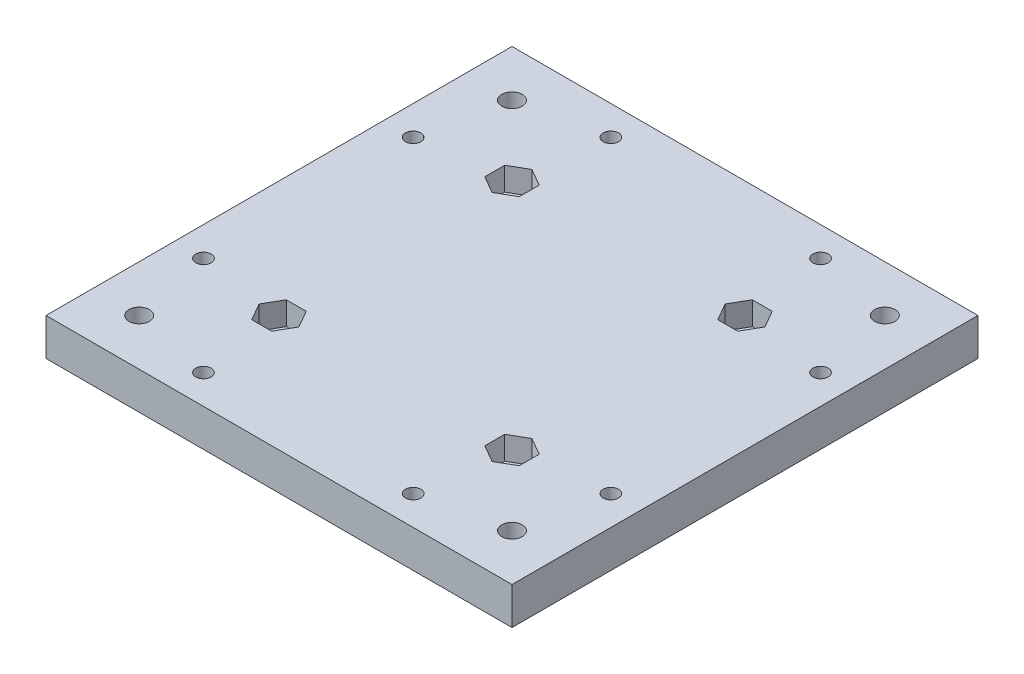
SolidWorks part; units mm, degrees
ref_plane "Front Plane" through (0, 0, 0) normal (0, 0, 1) x (1, 0, 0)
ref_plane "Top Plane" through (0, 0, 0) normal (0, 1, 0) x (1, 0, 0)
ref_plane "Right Plane" through (0, 0, 0) normal (1, 0, 0) x (0, 0, -1)
sketch "Sketch1" plane through (0, 0, 0) normal (0, 1, 0) x (1, 0, 0)
  line L0 (22.5, 43.7132) -> (43.7132, 22.5) construction
  line L1 (0, 0) -> (14.5501, 0) construction
  line L2 (28.7, -27.1362) -> (28.7, -22.8638)
  line L3 (27.1362, 28.7) -> (22.8638, 28.7)
  line L4 (22.8638, 28.7) -> (20.7276, 25)
  line L5 (20.7276, 25) -> (22.8638, 21.3)
  line L6 (22.8638, 21.3) -> (27.1362, 21.3)
  line L7 (27.1362, 21.3) -> (29.2724, 25)
  line L8 (29.2724, 25) -> (27.1362, 28.7)
  line L9 (42.1362, 36.3) -> (44.2724, 40)
  line L10 (44.2724, 40) -> (42.1362, 43.7)
  line L11 (42.1362, 43.7) -> (37.8638, 43.7)
  line L12 (37.8638, 43.7) -> (35.7276, 40)
  line L13 (35.7276, 40) -> (37.8638, 36.3)
  line L14 (37.8638, 36.3) -> (42.1362, 36.3)
  line L15 (28.7, -22.8638) -> (25, -20.7276)
  line L16 (25, -20.7276) -> (21.3, -22.8638)
  line L17 (21.3, -22.8638) -> (21.3, -27.1362)
  line L18 (21.3, -27.1362) -> (25, -29.2724)
  line L19 (25, -29.2724) -> (28.7, -27.1362)
  line L20 (36.3, -42.1362) -> (40, -44.2724)
  line L21 (40, -44.2724) -> (43.7, -42.1362)
  line L22 (43.7, -42.1362) -> (43.7, -37.8638)
  line L23 (43.7, -37.8638) -> (40, -35.7276)
  line L24 (40, -35.7276) -> (36.3, -37.8638)
  line L25 (36.3, -37.8638) -> (36.3, -42.1362)
  line L26 (-27.1362, -28.7) -> (-22.8638, -28.7)
  line L27 (-22.8638, -28.7) -> (-20.7276, -25)
  line L28 (-20.7276, -25) -> (-22.8638, -21.3)
  line L29 (-22.8638, -21.3) -> (-27.1362, -21.3)
  line L30 (-27.1362, -21.3) -> (-29.2724, -25)
  line L31 (-29.2724, -25) -> (-27.1362, -28.7)
  line L32 (-42.1362, -36.3) -> (-44.2724, -40)
  line L33 (-44.2724, -40) -> (-42.1362, -43.7)
  line L34 (-42.1362, -43.7) -> (-37.8638, -43.7)
  line L35 (-37.8638, -43.7) -> (-35.7276, -40)
  line L36 (-35.7276, -40) -> (-37.8638, -36.3)
  line L37 (-37.8638, -36.3) -> (-42.1362, -36.3)
  line L38 (-28.7, 27.1362) -> (-28.7, 22.8638)
  line L39 (-28.7, 22.8638) -> (-25, 20.7276)
  line L40 (-25, 20.7276) -> (-21.3, 22.8638)
  line L41 (-21.3, 22.8638) -> (-21.3, 27.1362)
  line L42 (-21.3, 27.1362) -> (-25, 29.2724)
  line L43 (-25, 29.2724) -> (-28.7, 27.1362)
  line L44 (-36.3, 42.1362) -> (-40, 44.2724)
  line L45 (-40, 44.2724) -> (-43.7, 42.1362)
  line L46 (-43.7, 42.1362) -> (-43.7, 37.8638)
  line L47 (-43.7, 37.8638) -> (-40, 35.7276)
  line L48 (-40, 35.7276) -> (-36.3, 37.8638)
  line L49 (-36.3, 37.8638) -> (-36.3, 42.1362)
  line L51 (-50, -50) -> (50, -50)
  line L52 (-50, -50) -> (-50, 50)
  line L53 (-50, 50) -> (50, 50)
  line L54 (50, -50) -> (50, 50)
  line L55 (-50, -50) -> (50, 50) construction
  line L56 (-50, 50) -> (50, -50) construction
  circle A0 centre (40, 40) radius 2.2
  circle A1 centre (43.7132, 22.5) radius 1.65
  circle A2 centre (22.5, 43.7132) radius 1.65
  circle A3 centre (25, 25) radius 2.15
  circle A4 centre (25, 25) radius 3.7 construction
  circle A5 centre (40, 40) radius 3.7 construction
  circle A6 centre (25, -25) radius 2.15
  circle A7 centre (22.5, -43.7132) radius 1.65
  circle A8 centre (40, -40) radius 2.2
  circle A9 centre (43.7132, -22.5) radius 1.65
  circle A10 centre (-25, -25) radius 2.15
  circle A11 centre (-43.7132, -22.5) radius 1.65
  circle A12 centre (-40, -40) radius 2.2
  circle A13 centre (-22.5, -43.7132) radius 1.65
  circle A14 centre (-25, 25) radius 2.15
  circle A15 centre (-22.5, 43.7132) radius 1.65
  circle A16 centre (-40, 40) radius 2.2
  circle A17 centre (-43.7132, 22.5) radius 1.65
  point P88 (0, 0)
  dimension "D3" = 4.4
  dimension "D6" = 3.3
  dimension "D7" = 3.3
  dimension "D8" = 30
  dimension "D10" = 4.3
  dimension "D1" = 40
  dimension "D2" = 40
  dimension "D4" = 22.5
  dimension "D5" = 22.5
  dimension "D9" = 45
  dimension "D11" = 25
  dimension "D12" = 25
  dimension "D13" = 7.4
  dimension "D14" = 7.4
  dimension "D16" = 100
  dimension "D15" = 4
extrude "Boss-Extrude1" add sketch "Sketch1" along normal blind 8 contours L51 L54 L53 L52 A17 A15 A13 A11 A9 A7 A2 A1 L8 L7 L6 L5 L4 L3 L14 L13 L12 L11 L10 L9 L19 L18 L17 L16 L15 L2 L25 L24 L23 L22 L21 L20 L31 L30 | L36 L37 L32 L33 L34 L35 A12 | L48 L49 L44 L45 L46 L47 A16 | L13 L14 L9 L10 L11 L12 A0 | L24 L25 L20 L21 L22 L23 A8 region at (40, 0, -36.413) region at (36.413, 0, 40) region at (-40, 0, 36.413) region at (-36.413, 0, -40) region at (0, 0, 0)
extrude "Boss-Extrude2" add sketch "Sketch1<3>" along normal blind 3 contours L42 L43 L38 L39 L40 L41 A14 | L7 L8 L3 L4 L5 L6 A3 | L30 L31 L26 L27 L28 L29 A10 | L18 L19 L2 L15 L16 L17 A6 region at (26.7935, 0, 28.1064) region at (28.1064, 0, -26.7935) region at (-28.1064, 0, 26.7935) region at (-26.7935, 0, -28.1064)
sketch "Sketch1<3>" plane through (0, 0, 0) normal (0, 1, 0) x (1, 0, 0) same geometry as "Sketch1"
extrude "Cut-Extrude1" cut sketch "Sketch1<4>" along normal blind 4 contours L36 L37 L32 L33 L34 L35 A12 | L24 L25 L20 L21 L22 L23 A8 | L13 L14 L9 L10 L11 L12 A0 | L48 L49 L44 L45 L46 L47 A16 region at (40, 0, -36.413) region at (36.413, 0, 40) region at (-40, 0, 36.413) region at (-36.413, 0, -40)
sketch "Sketch1<4>" plane through (0, 0, 0) normal (0, 1, 0) x (1, 0, 0) same geometry as "Sketch1"
chamfer "Chamfer1" distance 2 angle 45 8 edges at (22.5, 0, -42.0632) (43.7132, 0, -20.85) (43.7132, 0, 24.15) (22.5, 0, 45.3632) (-22.5, 0, 45.3632) (-43.7132, 0, 24.15) (-22.5, 0, -42.0632) (-43.7132, 0, -20.85)
